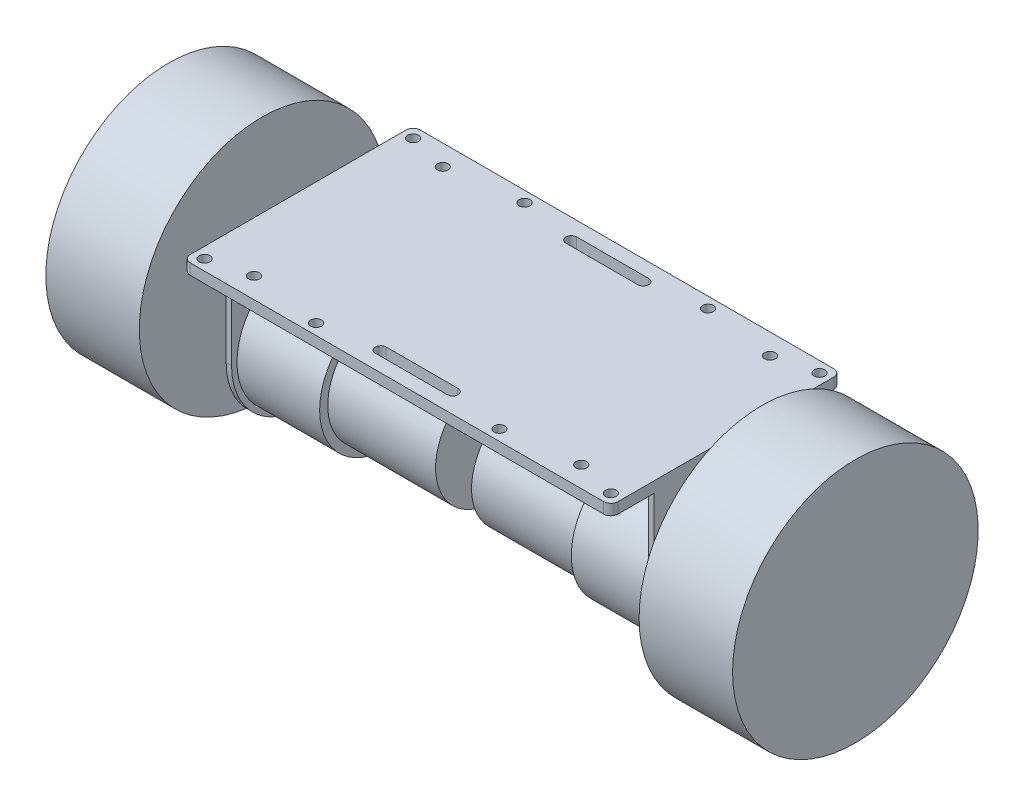
SolidWorks part; units mm, degrees
ref_plane "Front" through (0, 0, 0) normal (0, 0, 1) x (1, 0, 0)
ref_plane "Top" through (0, 0, 0) normal (0, 1, 0) x (1, 0, 0)
ref_plane "Right" through (0, 0, 0) normal (1, 0, 0) x (0, 0, -1)
sketch "Sketch2" plane through (0, 0, 0) normal (0, 1, 0) x (1, 0, 0)
  line L0 (0, 32) -> (0, -32) construction
  line L1 (57.5, -32) -> (-57.5, -32)
  line L2 (59.5, -30) -> (59.5, 30)
  line L3 (57.5, 32) -> (-57.5, 32)
  line L4 (-59.5, -30) -> (-59.5, 30)
  line L5 (59.5, -32) -> (-59.5, 32) construction
  line L6 (59.5, 32) -> (-59.5, -32) construction
  line L7 (59.5, 0) -> (-59.5, 0) construction
  line L8 (10, 28) -> (-10, 28)
  line L9 (-10, 25) -> (10, 25)
  line L10 (-10, -25) -> (10, -25)
  line L11 (10, -28) -> (-10, -28)
  arc A0 (57.5, -32) -> (59.5, -30) centre (57.5, -30) ccw
  arc A1 (59.5, 30) -> (57.5, 32) centre (57.5, 30) ccw
  arc A2 (-57.5, -32) -> (-59.5, -30) centre (-57.5, -30) cw
  arc A3 (-57.5, 32) -> (-59.5, 30) centre (-57.5, 30) ccw
  circle A4 centre (-56.5, 29) radius 1.5
  circle A5 centre (-45.5, 26.25) radius 1.5
  circle A6 centre (-25.5, 29) radius 1.5
  circle A7 centre (-25.5, -29) radius 1.5
  circle A8 centre (-45.5, -26.25) radius 1.5
  circle A9 centre (-56.5, -29) radius 1.5
  circle A10 centre (25.5, -29) radius 1.5
  circle A11 centre (45.5, -26.25) radius 1.5
  circle A12 centre (56.5, -29) radius 1.5
  circle A13 centre (56.5, 29) radius 1.5
  circle A14 centre (45.5, 26.25) radius 1.5
  circle A15 centre (25.5, 29) radius 1.5
  arc A16 (-10, 28) -> (-10, 25) centre (-10, 26.5) ccw
  arc A17 (10, 28) -> (10, 25) centre (10, 26.5) cw
  arc A18 (10, -28) -> (10, -25) centre (10, -26.5) ccw
  arc A19 (-10, -28) -> (-10, -25) centre (-10, -26.5) cw
  point P0 (0, 0)
  point P46 (0, 25)
  point P54 (0, 28)
  dimension "D3" = 2
  dimension "D4" = 3
  dimension "D7" = 3
  dimension "D10" = 4
  dimension "D13" = 10
  dimension "D1" = 64
  dimension "D2" = 119
  dimension "D5" = 3
  dimension "D6" = 3
  dimension "D8" = 5.75
  dimension "D9" = 3
  dimension "D11" = 34
  dimension "D12" = 14
extrude "Boss-Extrude1" add sketch "Sketch2" along normal blind 3
sketch "Sketch4" plane through (0, 0, 0) normal (0, -1, 0) x (1, 0, 0)
  line L0 (-59.5, 0) -> (59.5, 0) construction
  line L1 (-59.5, -30) -> (-59.5, 30) construction
  line L2 (59.5, 30) -> (59.5, -30) construction
  line L4 (-58, -20) -> (-59.5, -20)
  line L5 (-58, -20) -> (-58, 20)
  line L6 (-58, 20) -> (-59.5, 20)
  line L7 (-59.5, -20) -> (-59.5, 20)
  line L8 (-58, -20) -> (-59.5, 20) construction
  line L9 (-58, 20) -> (-59.5, -20) construction
  point P6 (-58.75, 0)
  dimension "D1" = 1.5
  dimension "D2" = 40
extrude "Boss-Extrude2" add sketch "Sketch4" along normal blind 48
mirror "Mirror3" about plane through (0, 0, 0) normal (1, 0, 0) of "Boss-Extrude2"
sketch "Sketch5" plane through (-59.5, 0, 0) normal (-1, 0, 0) x (0, 0, 1)
  line L0 (-20, -48) -> (-20, 0) construction
  line L1 (20, -48) -> (20, 0) construction
  line L2 (-20, -28) -> (20, -28) construction
  line L3 (20, -48) -> (-20, -48) construction
  line L4 (-20, -28) -> (-20, -48)
  line L5 (-20, -48) -> (20, -48)
  line L6 (20, -48) -> (20, -28)
  arc A0 (-20, -28) -> (20, -28) centre (0, -28) ccw
  line M4 (-20, 0) -> (-20, -48)
  line M5 (-20, -48) -> (20, -48)
  line M6 (20, -48) -> (20, 0)
extrude "Cut-Extrude1" cut sketch "Sketch5" against normal through all contours A0 M4 M5 | A0 L5 M6 region at (-59.5, -43.5326, -15.5326) region at (-59.5, -43.5326, 15.5326)
sketch "Sketch6" plane through (-58, 0, 0) normal (1, 0, 0) x (0, 0, -1)
  line L0 (-20, -28) -> (20, -28) construction
  circle A0 centre (0, -28) radius 18.5
  arc A1 (-20, -28) -> (20, -28) centre (0, -28) ccw construction
  dimension "D1" = 1.5
extrude "Boss-Extrude3" add sketch "Sketch6" along normal blind 23
sketch "Sketch7" plane through (-35, 0, 0) normal (1, 0, 0) x (0, 0, -1)
  circle A0 centre (0, -28) radius 16.25
extrude "Boss-Extrude4" add sketch "Sketch7" along normal blind 30
sketch "Sketch8" plane through (-59.5, 0, 0) normal (-1, 0, 0) x (0, 0, 1)
  line L0 (0, 3) -> (0, -48) construction
  line L1 (-30, 3) -> (30, 3) construction
  line L2 (-20, -18) -> (20, -18) construction
  line L3 (-20, -28) -> (-20, 0) construction
  line L4 (20, -28) -> (20, 0) construction
  arc A0 (-20, -28) -> (20, -28) centre (0, -28) ccw construction
  circle A1 centre (0, -18) radius 6
  point P13 (0, -18)
  dimension "D2" = 12
  dimension "D1" = 21
extrude "Boss-Extrude5" add sketch "Sketch8" along normal blind 10
sketch "Sketch9" plane through (-69.5, 0, 0) normal (-1, 0, 0) x (0, 0, 1)
  circle A0 centre (0, -18) radius 34.15
  dimension "D1" = 68.3
extrude "Boss-Extrude6" add sketch "Sketch9" along normal blind 26
mirror "Mirror7" about plane through (0, 0, 0) normal (1, 0, 0) of "Boss-Extrude5", "Boss-Extrude6", "Boss-Extrude4", "Boss-Extrude3"
